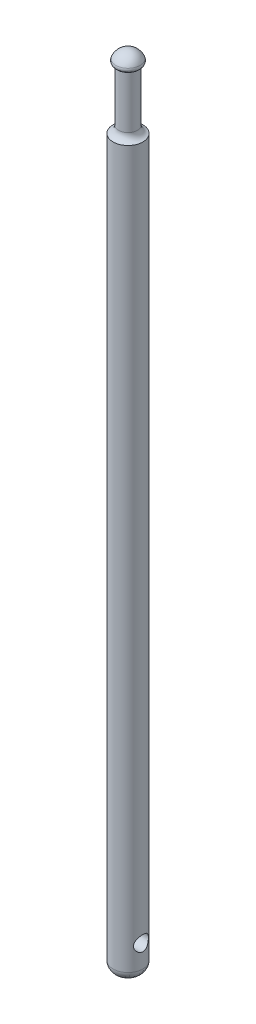
SolidWorks part; units mm, degrees
ref_plane "Front Plane" through (0, 0, 0) normal (0, 0, 1) x (1, 0, 0)
ref_plane "Top Plane" through (0, 0, 0) normal (0, 1, 0) x (1, 0, 0)
ref_plane "Right Plane" through (0, 0, 0) normal (1, 0, 0) x (0, 0, -1)
sketch "Sketch1" plane through (0, 0, 0) normal (0, 1, 0) x (1, 0, 0)
  circle A0 centre (0, 0) radius 2
  dimension "D1" = 4
extrude "Boss-Extrude1" add sketch "Sketch1" along normal blind 104
dome "Dome2" faces to dome 1 distance 1.5 reverse direction no elliptical dome yes face at (0, 0, 2) parameters "D1"=1.5
sketch "Sketch2" plane through (0, 0, 0) normal (1, 0, 0) x (0, 0, -1)
  circle A0 centre (0, 3) radius 1
  point P3 (0, 0)
  dimension "D1" = 2
  dimension "D2" = 3
extrude "Cut-Extrude1" cut sketch "Sketch2" against normal through all both and the other way through all
sketch "Sketch4" plane through (0, 0, 0) normal (0, 1, 0) x (1, 0, 0)
  circle A0 centre (0, 0) radius 1.25
  dimension "D1" = 2.5
sketch "Sketch5" plane through (0, 0, 0) normal (0, 0, 1) x (1, 0, 0)
  line L1 (0, 102.25) -> (0, 105.75)
  line L2 (2, 104) -> (-2, 104) construction
  arc A0 (0, 102.25) -> (0, 105.75) centre (0, 104) ccw
  point P1 (0, 0)
  point P2 (0, 109.0523)
  point P6 (0, 105)
  point P7 (0, 0)
  dimension "D1" = 3.5
revolve "Revolve1" add sketch "Sketch5" angle 360 about L1
sketch "Sketch6" plane through (0, 0, 0) normal (0, 0, 1) x (1, 0, 0)
  line L0 (0, 105.75) -> (0, 91.3019) construction
  line L1 (2, 104) -> (1.25, 104)
  line L2 (2, 104) -> (2, 96)
  line L3 (2, 96) -> (1.25, 96)
  line L4 (1.25, 104) -> (1.25, 96)
  arc A0 (1.75, 104) -> (-1.75, 104) centre (0, 104) ccw construction
  dimension "D1" = 8
  dimension "D2" = 0.75
revolve "Cut-Revolve1" cut sketch "Sketch6" angle 360 about L0
fillet "Fillet1" radius 0.5 1 edges at (1.75, 104, 0)
fillet "Fillet2" radius 1 1 edges at (-1.25, 96, 0)
